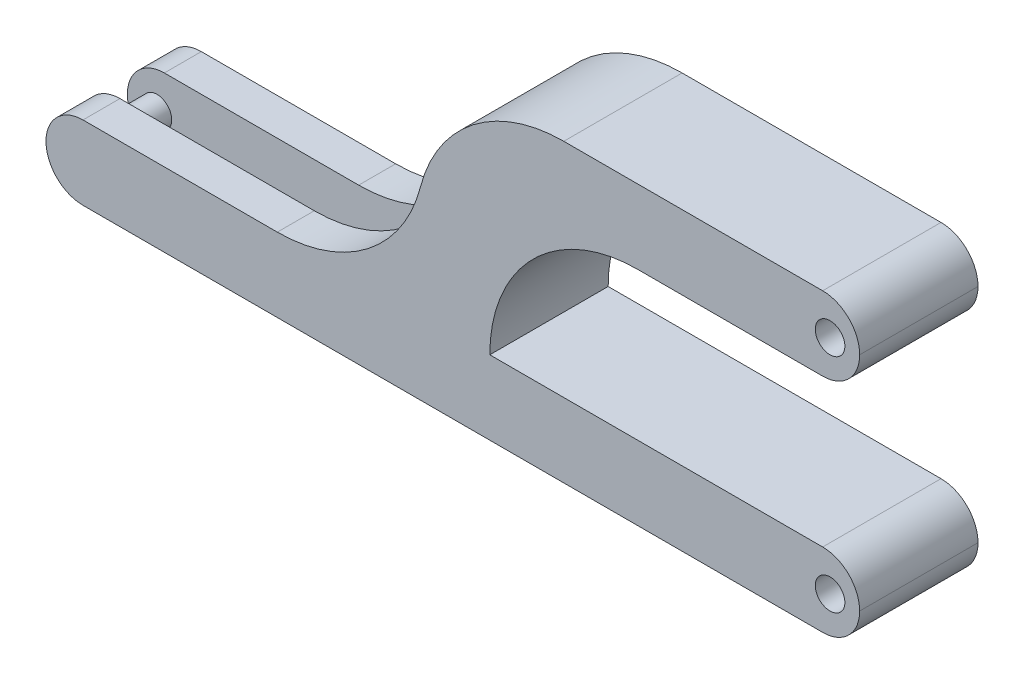
SolidWorks part; units mm, degrees
material "Hexcel AS4C (3000 Filaments)"
ref_plane "Front Plane" through (0, 0, 0) normal (0, 0, 1) x (1, 0, 0)
ref_plane "Top Plane" through (0, 0, 0) normal (0, 1, 0) x (1, 0, 0)
ref_plane "Right Plane" through (0, 0, 0) normal (1, 0, 0) x (0, 0, -1)
sketch "Sketch1" plane through (0, 0, 0) normal (0, 0, 1) x (1, 0, 0)
  line L0 (-95.5556, 0) -> (0, 0) construction
  line L1 (60, 20) -> (0, 20)
  line L2 (0, 20) -> (0, 0)
  line L3 (60, 10) -> (10, 10)
  line L4 (10, 10) -> (10, 0)
  line L6 (60, 10) -> (60, 20)
  line L7 (60, -10) -> (10, -10)
  line L8 (10, -10) -> (10, 0)
  line L9 (0, -20) -> (0, 0)
  line L10 (60, -20) -> (0, -20)
  line L11 (60, -10) -> (60, -20)
  line L12 (10, 0) -> (131.1111, 0) construction
  line L13 (56, 20) -> (56, -20) construction
  line L14 (60, 15) -> (56, 15) construction
  line L15 (60, -15) -> (56, -15) construction
  circle A0 centre (56, 15) radius 2
  circle A1 centre (56, -15) radius 2
  dimension "D5" = 4
  dimension "D1" = 20
  dimension "D2" = 60
  dimension "D4" = 4
  dimension "D3" = 10
extrude "Boss-Extrude1" add sketch "Sketch1" along normal blind 8
sketch "Sketch2" plane through (0, 0, 0) normal (-1, 0, 0) x (0, 0, 1)
  line L1 (8, -20) -> (3, -20)
  line L2 (8, -20) -> (8, -10)
  line L3 (8, -10) -> (3, -10)
  line L4 (3, -20) -> (3, -10)
  dimension "D1" = 5
  dimension "D2" = 10
extrude "Boss-Extrude2" add sketch "Sketch2" along normal blind 50
sketch "Sketch3" plane through (0, 0, 3) normal (0, 0, -1) x (-1, 0, 0)
  line L0 (46, -10) -> (46, -20) construction
  line L2 (50, -10) -> (0, -10) construction
  line L3 (50, -20) -> (0, -20) construction
  line L4 (50, -10) -> (50, -20) construction
  circle A0 centre (46, -15) radius 2
  dimension "D2" = 4
  dimension "D1" = 4
extrude "Boss-Extrude3" add sketch "Sketch3" along normal blind 5
mirror "Mirror1" about plane through (0, 0, 0) normal (0, 0, 1) of "Boss-Extrude1", "Boss-Extrude2", "Boss-Extrude3"
fillet "Fillet1" radius 20 1 edges at (10, 10, 0)
fillet "Fillet2" radius 20 1 edges at (0, 20, 0)
fillet "Fillet3" radius 20 2 edges at (0, -10, 5.5) (0, -10, -5.5)
fillet "Fillet4" radius 5 8 edges at (-50, -20, -5.5) (-50, -10, -5.5) (-50, -20, 5.5) (-50, -10, 5.5) (60, 20, 0) (60, 10, 0) (60, -20, 0) (60, -10, 0)
